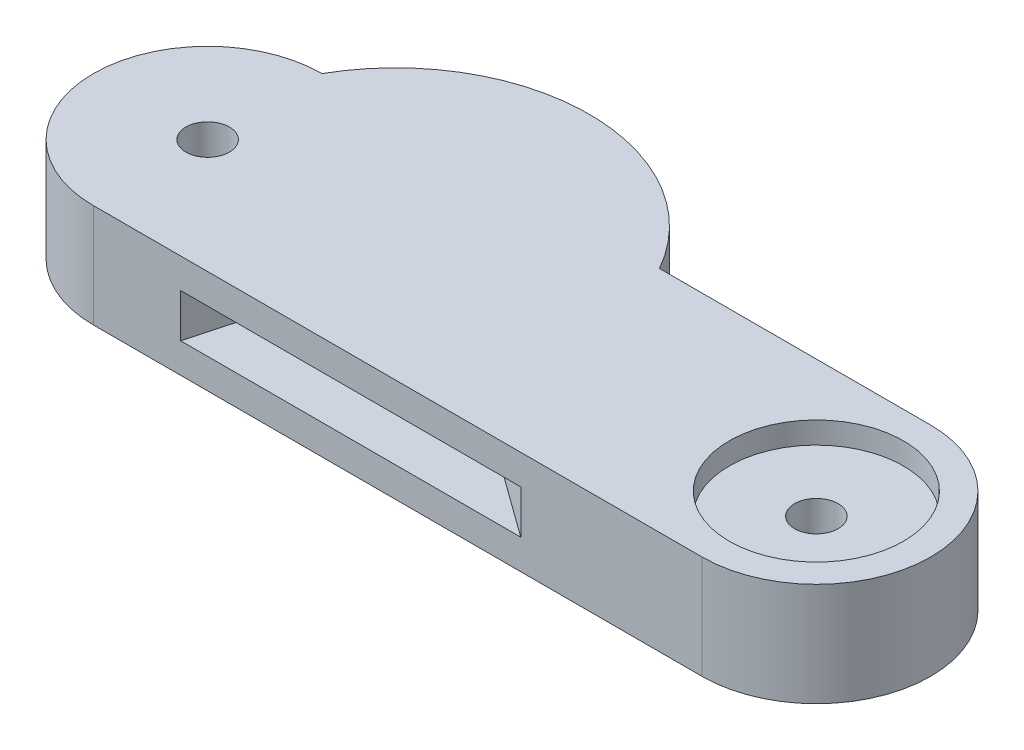
SolidWorks part; units mm, degrees
ref_plane "Front Plane" through (0, 0, 0) normal (0, 0, 1) x (1, 0, 0)
ref_plane "Top Plane" through (0, 0, 0) normal (0, 1, 0) x (1, 0, 0)
ref_plane "Right Plane" through (0, 0, 0) normal (1, 0, 0) x (0, 0, -1)
sketch "Sketch1" plane through (0, 0, 0) normal (0, 1, 0) x (1, 0, 0)
  line L0 (0, -10.5004) -> (-55.9305, -10.5004)
  line L1 (0, 10.5004) -> (-55.9305, 10.5004)
  line L5 (0, 11.5004) -> (-55.9305, 11.5004) construction
  line L6 (0, -11.5004) -> (-55.9305, -11.5004) construction
  circle A0 centre (0, 0) radius 2
  arc A1 (0, -10.5004) -> (0, 10.5004) centre (0, 0) ccw
  arc A2 (-55.9305, 10.5004) -> (-55.9305, -10.5004) centre (-55.9305, 0) ccw
  circle A3 centre (-55.9305, 0) radius 2
  arc A7 (0, -11.5004) -> (0, 11.5004) centre (0, 0) ccw construction
  arc A8 (-55.9305, 11.5004) -> (-55.9305, -11.5004) centre (-55.9305, 0) ccw construction
  arc A9 (-55.2376, -38.6748) -> (-39.2208, -41.4996) centre (-45.8168, -32.0788) ccw construction
  arc A10 (-55.9305, 10.5004) -> (-55.9305, -10.5004) centre (-55.9305, 0) ccw construction
  circle A11 centre (0, 0) radius 67.4309 construction
  arc A12 (-67.3132, -3.9833) -> (-55.2376, -38.6748) centre (0, 0) ccw construction
  dimension "D1" = 4
  dimension "D2" = 1
  dimension "D3" = 4
extrude "Boss-Extrude1" add sketch "Sketch1" along normal mid plane 9.5
sketch "Sketch3" plane through (0, 0, 0) normal (0, 1, 0) x (1, 0, 0)
  line L0 (0, 0) -> (-47.1525, -15.3208) construction
  line L1 (0, 0) -> (24.7895, -42.9367) construction
  line L2 (0, 0) -> (-55.9305, 0) construction
  line L3 (24.7895, -42.9367) -> (-41.5934, 5.0595) construction
  line L4 (-41.5934, 5.0595) -> (-47.1525, -15.3208) construction
  line L5 (-41.5934, 5.0595) -> (-37.6461, 19.5308) construction
  line L6 (-41.5934, 5.0595) -> (-53.749, 13.8482) construction
  line L7 (22.8477, -44.0007) -> (-38.0092, 0) construction
  line L8 (-35.7518, 18.8753) -> (-39.2995, 5.869)
  line L9 (-43.8873, 4.25) -> (-54.8123, 12.149)
  line L11 (26.6452, -41.8104) -> (-39.2995, 5.869)
  line L12 (-39.6108, 19.9279) -> (-42.7627, 8.3729) construction
  line L13 (-42.7627, 8.3729) -> (-52.4686, 15.3905) construction
  line L14 (-40.9004, 0) -> (-45.9674, -18.5763) construction
  line L15 (-43.8873, 4.25) -> (-48.2065, -11.585)
  line L18 (-40.4216, 6.6802) -> (-50.8477, 14.2185) construction
  line L20 (-41.5934, 5.0595) -> (-52.0196, 12.5978) construction
  line L21 (-42.7652, 3.4387) -> (-53.1914, 10.977) construction
  line L23 (-43.5229, 5.5858) -> (-49.082, -14.7945) construction
  line L26 (-39.6639, 4.5332) -> (-45.223, -15.8471) construction
  line L27 (25.9613, -41.316) -> (-40.4216, 6.6802) construction
  line L28 (23.6177, -44.5574) -> (-42.7652, 3.4387) construction
  arc A1 (-48.2065, -11.585) -> (26.6452, -41.8104) centre (0, 0) ccw
  arc A4 (-55.9305, 10.5004) -> (-55.9305, -10.5004) centre (-55.9305, 0) ccw construction
  arc A7 (-35.7518, 18.8753) -> (-54.8123, 12.149) centre (-41.5934, 5.0595) ccw
  dimension "D1" = 99.1581
  dimension "D3" = 120
  dimension "D6" = 30
  dimension "D2" = 18
  dimension "D4" = 2
  dimension "D5" = 2
extrude "Cut-Extrude1" cut sketch "Sketch3" against normal mid plane 4
sketch "Sketch5" plane through (0, 0, 0) normal (0, 1, 0) x (1, 0, 0)
  line L0 (-40.4241, 1.7461) -> (-52.5322, 10.5004) construction
  line L1 (-40.4241, 1.7461) -> (-35.7382, 18.9254) construction
  line L2 (-52.5322, 10.5004) -> (-43.8873, 4.25) construction
  line L3 (-39.2995, 5.869) -> (-38.0362, 10.5004) construction
  line L4 (-55.9305, 10.5004) -> (-24.9177, 10.5004)
  line L5 (0, 10.5004) -> (-55.9305, 10.5004) construction
  circle A0 centre (-40.4241, 1.7461) radius 17.807
extrude "Boss-Extrude2" add sketch "Sketch5" along normal up to surface and the other way up to surface contours A0 region at (-40.4241, 0, -14.2141) up to face at (0, 4.75, 2) other way up to face at (-27.9653, -4.75, 0)
sketch "Sketch6" plane through (0, 0, 0) normal (0, 1, 0) x (1, 0, 0)
  line L0 (-39.2995, 5.869) -> (-16.6593, -10.5004)
  line L1 (-47.9107, -10.5004) -> (-43.8873, 4.25)
  line L2 (-43.8873, 4.25) -> (-54.8544, 12.1794)
  line L3 (-39.2995, 5.869) -> (-35.7382, 18.9254)
  line L4 (-16.6593, -10.5004) -> (-39.2995, 5.869) construction
  line L5 (-43.8873, 4.25) -> (-47.9107, -10.5004) construction
  line L6 (-52.5322, 10.5004) -> (-43.8873, 4.25) construction
  line L7 (-39.2995, 5.869) -> (-38.0362, 10.5004) construction
  line L8 (-55.9305, -10.5004) -> (0, -10.5004) construction
  line L9 (-16.6593, -10.5004) -> (-47.9107, -10.5004)
  arc A0 (-24.9177, 10.5004) -> (-55.9305, 10.5004) centre (-40.4241, 1.7461) ccw construction
  arc A1 (-35.7382, 18.9254) -> (-54.8544, 12.1794) centre (-40.4241, 1.7461) ccw
extrude "Cut-Extrude2" cut sketch "Sketch6" against normal mid plane 4
sketch "Sketch7" plane through (0, 4.75, 0) normal (0, 1, 0) x (1, 0, 0)
  circle A0 centre (0, 0) radius 8
  dimension "D1" = 16
extrude "Cut-Extrude3" cut sketch "Sketch7" against normal blind 2
ref_plane "Plane1" through (0, 0, 0) normal (0, 1, 0) x (1, 0, 0)
